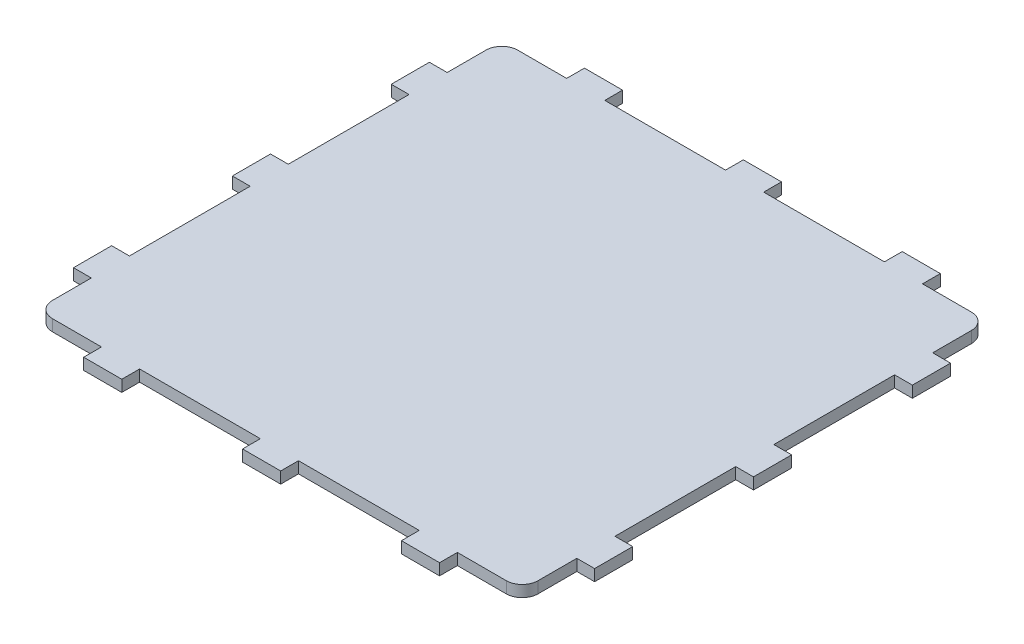
SolidWorks part; units mm, degrees
ref_plane "前视基准面" through (0, 0, 0) normal (0, 0, 1) x (1, 0, 0)
ref_plane "上视基准面" through (0, 0, 0) normal (0, 1, 0) x (1, 0, 0)
ref_plane "右视基准面" through (0, 0, 0) normal (1, 0, 0) x (0, 0, -1)
other "Configuration Table"
sketch "草图1" plane through (0, 0, 0) normal (0, 1, 0) x (1, 0, 0)
  line L1 (-382, 366) -> (382, 366)
  line L2 (-382, 366) -> (-382, -366)
  line L3 (-382, -366) -> (382, -366)
  line L4 (382, 366) -> (382, -366)
  line L5 (-410, -220) -> (-382, -220)
  line L6 (-410, -220) -> (-410, -280)
  line L7 (-410, -280) -> (-382, -280)
  line L8 (-382, -220) -> (-382, -280)
  line L9 (-280, -394) -> (-220, -394)
  line L10 (-280, -394) -> (-280, -366)
  line L11 (-280, -366) -> (-220, -366)
  line L12 (-220, -394) -> (-220, -366)
  point P4 (-382, 0)
  point P6 (0, -366)
  point P11 (-410, -250)
  point P18 (-277.167, -384)
  dimension "D1" = 764
  dimension "D2" = 732
  dimension "D3" = 116
  dimension "D4" = 28
  dimension "D5" = 60
  dimension "D8" = 60
  dimension "D9" = 28
  dimension "D10" = 102
extrude "凸台-拉伸1" add sketch "草图1" along normal blind 18 contours L2 L3 L4 L1
extrude "凸台-拉伸2" add sketch "草图1<3>" along normal up to surface (18 mm away) contours L6 L7 L8 L5 up to face at (0, 18, 0)
sketch "草图1<3>" plane through (0, 0, 0) normal (0, 1, 0) x (1, 0, 0) same geometry as "草图1"
pattern_linear "阵列(线性)1" count 3 spacing 250 along (0, 0, -1) of "凸台-拉伸2"
mirror "镜向1" about plane through (0, 0, 0) normal (1, 0, 0) of "阵列(线性)1", "凸台-拉伸2"
extrude "凸台-拉伸3" add sketch "草图1<5>" along normal up to surface (18 mm away) contours L9 L12 L11 L10 up to face at (0, 18, 0)
sketch "草图1<5>" plane through (0, 0, 0) normal (0, 1, 0) x (1, 0, 0) same geometry as "草图1"
pattern_linear "阵列(线性)2" count 3 spacing 250 along (1, 0, 0) of "凸台-拉伸3"
mirror "镜向2" about plane through (0, 0, 0) normal (0, 0, 1) of "阵列(线性)2", "凸台-拉伸3"
fillet "圆角1" radius 25 4 edges at (-382, 9, -366) (382, 9, -366) (382, 9, 366) (-382, 9, 366)
